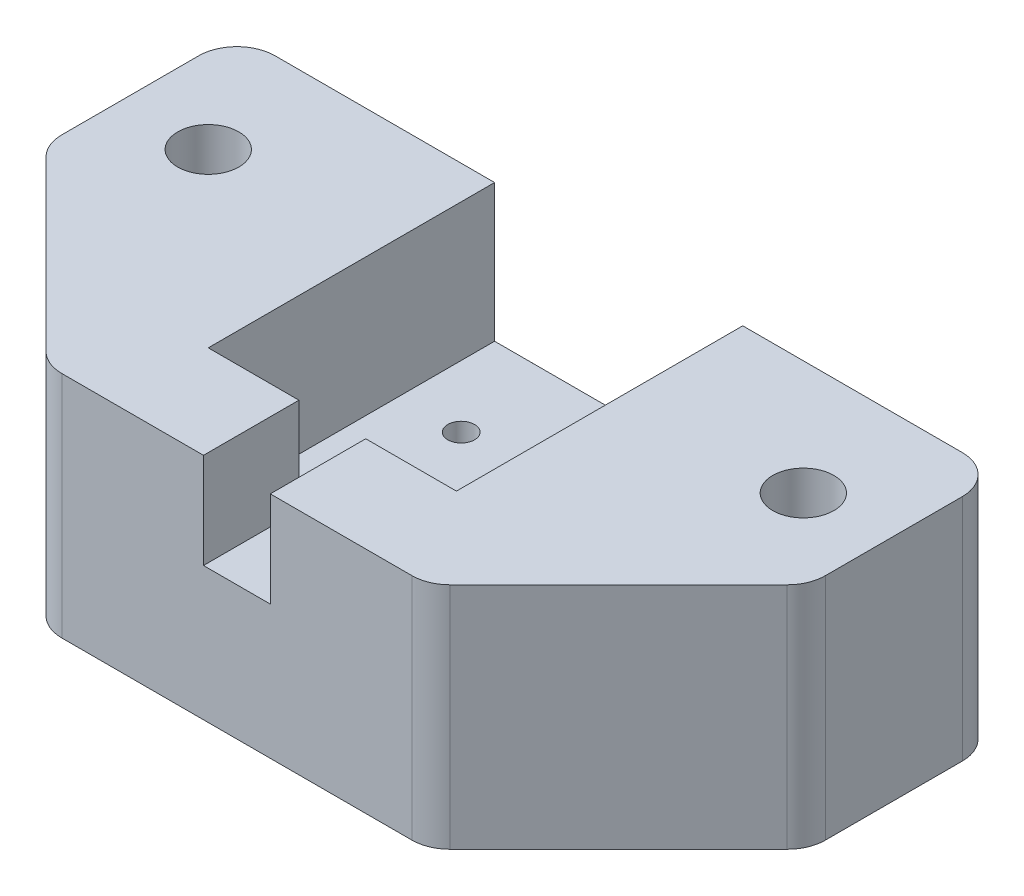
SolidWorks part; units mm, degrees
ref_plane "前视基准面" through (0, 0, 0) normal (0, 0, 1) x (1, 0, 0)
ref_plane "上视基准面" through (0, 0, 0) normal (0, 1, 0) x (1, 0, 0)
ref_plane "右视基准面" through (0, 0, 0) normal (1, 0, 0) x (0, 0, -1)
other "Configuration Table"
sketch "草图1" plane through (0, 0, 0) normal (0, 1, 0) x (1, 0, 0)
  line L1 (0, 0) -> (40, 0)
  line L2 (0, 0) -> (0, -20)
  line L3 (0, -20) -> (40, -20)
  line L4 (40, 0) -> (40, -20)
  circle A0 centre (4.5, -6) radius 1.6
  circle A1 centre (35.6729, -6) radius 1.6
  dimension "D3" = 3.2
  dimension "D4" = 3.2
  dimension "D1" = 40
  dimension "D2" = 20
  dimension "D5" = 35.6729
  dimension "D6" = 4.5
  dimension "D7" = 6
  dimension "D8" = 6
extrude "凸台-拉伸1" add sketch "草图1" along normal blind 12
sketch "草图2" plane through (0, 12, 0) normal (0, 1, 0) x (1, 0, 0)
  line L5 (0, 0) -> (0, -20) construction
  line L6 (40, 0) -> (0, 0) construction
  line L8 (13.5, 0) -> (26.5, 0)
  line L9 (13.5, 0) -> (13.5, -15)
  line L10 (13.5, -15) -> (26.5, -15)
  line L11 (26.5, 0) -> (26.5, -15)
  dimension "D4" = 15
  dimension "D5" = 13
  dimension "D6" = 13.5
extrude "切除-拉伸1" cut sketch "草图2" against normal blind 7.2
sketch "草图3" plane through (0, 12, 0) normal (0, 1, 0) x (1, 0, 0)
  line L0 (13.5, -15) -> (26.5, -15) construction
  line L1 (18.25, -15) -> (21.75, -15)
  line L2 (18.25, -15) -> (18.25, -20)
  line L3 (18.25, -20) -> (21.75, -20)
  line L4 (21.75, -15) -> (21.75, -20)
  line L5 (0, -20) -> (40, -20) construction
  line L6 (0, 0) -> (0, -20) construction
  dimension "D1" = 3.5
  dimension "D2" = 18.25
extrude "切除-拉伸2" cut sketch "草图3" against normal blind 5
chamfer "倒角1" distance 10 angle 45 2 edges at (40, 6, 20) (0, 6, 20)
fillet "圆角1" radius 2 6 edges at (0, 6, 0) (0, 6, 10) (10, 6, 20) (30, 6, 20) (40, 6, 10) (40, 6, 0)
sketch "草图4" plane through (0, 4.8, 0) normal (0, 1, 0) x (1, 0, 0)
  line L0 (26.5, 0) -> (13.5, 0) construction
  line L1 (13.5, 0) -> (13.5, -15) construction
  circle A0 centre (16.75, -5) radius 0.7
  circle A1 centre (23.25, -5) radius 0.7
  dimension "D1" = 1.4
  dimension "D2" = 1.4
  dimension "D3" = 5
  dimension "D4" = 5
  dimension "D5" = 6.5
  dimension "D6" = 3.25
extrude "切除-拉伸3" cut sketch "草图4" against normal through all
sketch "草图5" plane through (0, 0, 0) normal (0, -1, 0) x (-1, 0, 0)
  circle A0 centre (-35.6729, -6) radius 3
  circle A1 centre (-4.5, -6) radius 3
  dimension "D1" = 6
  dimension "D2" = 6
extrude "切除-拉伸4" cut sketch "草图5" against normal blind 4
chamfer "倒角2" distance 2 angle 45 2 edges at (35.6729, 4, 4.4) (4.5, 4, 4.4)
equation "\"D6@草图1\"=20-31/2"
equation "\"D6@草图2\"=20-13/2"
equation "\"D2@草图3\"=20-3.5/2"
equation "\"D6@草图4\"=6.5/2"
